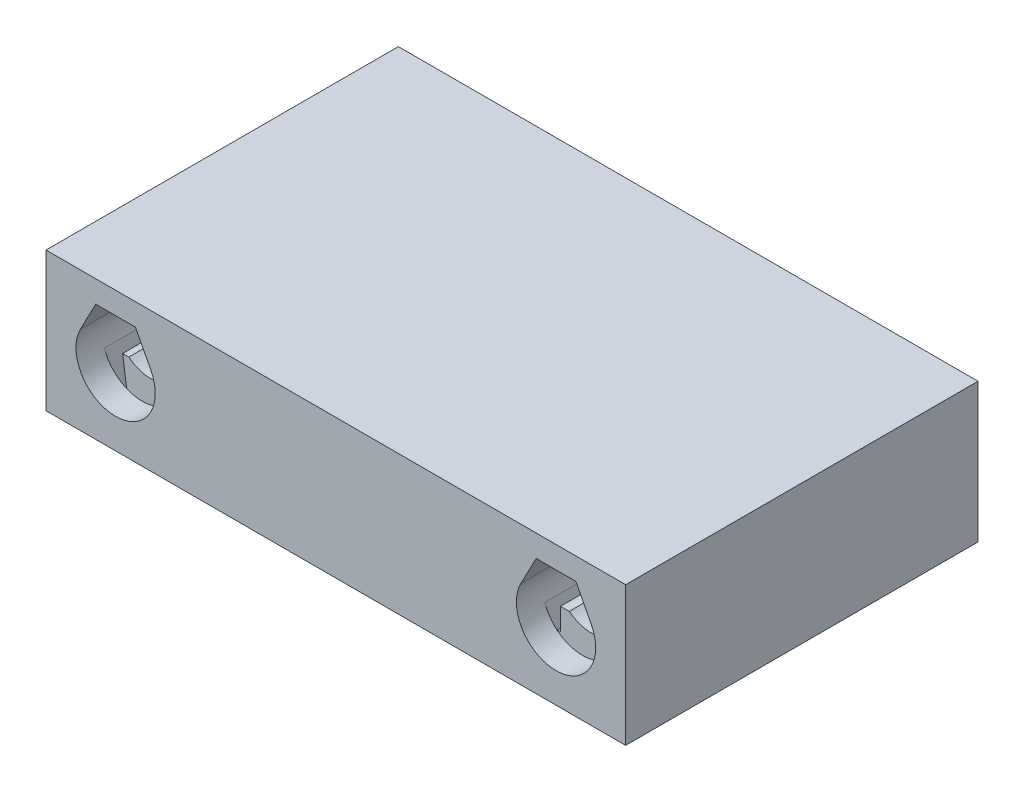
SolidWorks part; units mm, degrees
ref_plane "Piano frontale" through (0, 0, 0) normal (0, 0, 1) x (1, 0, 0)
ref_plane "Piano superiore" through (0, 0, 0) normal (0, 1, 0) x (1, 0, 0)
ref_plane "Piano destro" through (0, 0, 0) normal (1, 0, 0) x (0, 0, -1)
sketch "Schizzo2" plane through (0, 0, 0) normal (0, 0, 1) x (1, 0, 0)
  line L0 (-25, -4.5) -> (-25, 5.4) construction
  line L1 (-32.9, -7.9) -> (32.9, -7.9)
  line L2 (-32.9, -7.9) -> (-32.9, 7.9)
  line L3 (-32.9, 7.9) -> (32.9, 7.9)
  line L4 (32.9, -7.9) -> (32.9, 7.9)
  line L5 (-32.9, -7.9) -> (32.9, 7.9) construction
  line L6 (-32.9, 7.9) -> (32.9, -7.9) construction
  line L7 (0, 7.9) -> (0, -7.9) construction
  line L8 (-27.25, 5.4) -> (-22.75, 5.4)
  line L9 (-27.25, 5.4) -> (-28.9855, 2.0894)
  line L10 (-22.75, 5.4) -> (-21.0145, 2.0894)
  line L11 (27.25, 5.4) -> (22.75, 5.4)
  line L12 (22.75, 5.4) -> (21.0145, 2.0894)
  line L13 (27.25, 5.4) -> (28.9855, 2.0894)
  arc A0 (-28.9855, 2.0894) -> (-21.0145, 2.0894) centre (-25, 0) ccw
  arc A1 (28.9855, 2.0894) -> (21.0145, 2.0894) centre (25, 0) cw
  point P0 (0, 0)
  point P14 (-25, 5.4)
  dimension "D3" = 9
  dimension "D1" = 65.8
  dimension "D2" = 15.8
  dimension "D4" = 7.9
  dimension "D5" = 5.4
  dimension "D6" = 4.5
extrude "Front" add sketch "Schizzo2" along normal mid plane 3 contours L3 L4 L1 L2 | A0 L10 L8 L9 | A1 L12 L11 L13
sketch "Schizzo5" plane through (0, 0, -1.5) normal (0, 0, -1) x (-1, 0, 0)
  line L0 (-25, 5.4) -> (-25, -4.5) construction
  line L1 (-27.25, 5.4) -> (-22.75, 5.4) construction
  line L2 (-27.5, -1.9225) -> (-22.5, -1.9225) construction
  line L3 (-25, -4.5) -> (-25, -7.9) construction
  line L4 (32.9, -7.9) -> (-32.9, -7.9) construction
  line L5 (-25, -7.9) -> (-27.3599, -7.9)
  line L6 (-27.3599, -7.9) -> (-28.2, -1.9225)
  line L7 (-28.2, -1.9225) -> (-27.5, -1.9225)
  line L8 (-22.5, -1.9225) -> (-21.5, -1.9225)
  line L9 (-21.5, -1.9225) -> (-21.5, -4.4225)
  line L10 (-21.5, -4.4225) -> (-21.15, -4.4225)
  line L11 (-21.15, -4.4225) -> (-21.6387, -7.9) construction
  line L12 (-21.6387, -7.9) -> (-25, -7.9)
  line L13 (-28.3599, -7.9) -> (-29.271, -1.4172)
  line L14 (-21.15, -4.4225) -> (-20.7266, -1.4101)
  line L15 (0, -7.9) -> (0, 7.9) construction
  line L16 (32.9, 7.9) -> (-32.9, 7.9) construction
  line L17 (32.9, 7.9) -> (-32.9, 7.9)
  line L18 (-32.9, 7.9) -> (-32.9, -7.9)
  line L19 (-32.9, -7.9) -> (-28.3599, -7.9)
  line L20 (-21.6387, -7.9) -> (21.6387, -7.9)
  line L21 (-27.25, 5.4) -> (-28.9855, 2.0894) construction
  line L22 (-22.75, 5.4) -> (-21.0145, 2.0894) construction
  line L23 (-27.25, 5.4) -> (-28.9855, 2.0894)
  line L24 (-27.25, 5.4) -> (-22.75, 5.4)
  line L25 (-22.75, 5.4) -> (-21.0145, 2.0894)
  line L26 (21.15, -4.4225) -> (21.6387, -7.9) construction
  line L27 (25, -4.5) -> (25, -7.9) construction
  line L28 (27.5, -1.9225) -> (22.5, -1.9225) construction
  line L29 (25, 5.4) -> (25, -4.5) construction
  line L30 (22.75, 5.4) -> (21.0145, 2.0894)
  line L31 (27.25, 5.4) -> (22.75, 5.4)
  line L32 (27.25, 5.4) -> (28.9855, 2.0894)
  line L33 (32.9, -7.9) -> (28.3599, -7.9)
  line L34 (32.9, 7.9) -> (32.9, -7.9)
  line L35 (21.15, -4.4225) -> (20.7266, -1.4101)
  line L36 (28.3599, -7.9) -> (29.271, -1.4172)
  line L37 (21.6387, -7.9) -> (25, -7.9)
  line L38 (21.5, -4.4225) -> (21.15, -4.4225)
  line L39 (21.5, -1.9225) -> (21.5, -4.4225)
  line L40 (22.5, -1.9225) -> (21.5, -1.9225)
  line L41 (28.2, -1.9225) -> (27.5, -1.9225)
  line L42 (27.3599, -7.9) -> (28.2, -1.9225)
  line L43 (25, -7.9) -> (27.3599, -7.9)
  arc A0 (-28.9855, 2.0894) -> (-21.0145, 2.0894) centre (-25, 0) ccw construction
  arc A1 (-28.9855, 2.0894) -> (-21.0145, 2.0894) centre (-25, 0) ccw construction
  arc A2 (-27.5, -1.9225) -> (-22.5, -1.9225) centre (-25, 1.2) ccw
  arc A3 (-21.0145, 2.0894) -> (-20.7266, -1.4101) centre (-25, 0) cw
  arc A4 (28.9855, 2.0894) -> (29.271, -1.4172) centre (25, 0) cw construction
  arc A5 (21.0145, 2.0894) -> (20.7266, -1.4101) centre (25, 0) ccw
  arc A6 (27.5, -1.9225) -> (22.5, -1.9225) centre (25, 1.2) cw
  arc A7 (-28.9855, 2.0894) -> (-29.271, -1.4172) centre (-25, 0) ccw
  arc A8 (28.9855, 2.0894) -> (29.271, -1.4172) centre (25, 0) cw
  arc A9 (20.7266, -1.4101) -> (21.0145, 2.0894) centre (25, 0) cw construction
  point P12 (-25, -1.9225)
  point P55 (25, -1.9225)
  dimension "D1" = 8
  dimension "D2" = 1.2
  dimension "D3" = 98
  dimension "D4" = 0.7
  dimension "D5" = 1
  dimension "D6" = 2.5
  dimension "D7" = 5
  dimension "D8" = 0.35
  dimension "D9" = 98
  dimension "D10" = 1
  dimension "D11" = 98
extrude "Inner" add sketch "Schizzo5" along normal blind 34
sketch "Schizzo13" plane through (0, 0, -1.5) normal (0, 0, 1) x (1, 0, 0)
  line L0 (-21.5, -2.8284) -> (-21.5, -4.4225) construction
  line L1 (-21.5, -4.4225) -> (-21.15, -4.4225) construction
  line L2 (-27.3599, -7.9) -> (-27.9986, -3.3553) construction
  line L3 (-21.5, -2.8284) -> (-21.5, -4.4225)
  line L4 (-28.2, -1.9225) -> (-27.9986, -3.3553)
  line L5 (-21.5, -2.8284) -> (-21.5, -1.9225)
  line L6 (-21.5, -1.9225) -> (-22.5, -1.9225)
  line L7 (-27.5, -1.9225) -> (-28.2, -1.9225)
  line L8 (-28.2, -1.9225) -> (-27.9986, -3.3553)
  line L9 (-21.5, -2.8284) -> (-21.5, -1.9225)
  line L10 (-21.5, -1.9225) -> (-22.5, -1.9225)
  line L11 (-27.5, -1.9225) -> (-28.2, -1.9225)
  line L12 (-21.5, -4.4225) -> (-21.15, -4.4225)
  line L13 (-27.3599, -7.9) -> (-27.9986, -3.3553)
  line L14 (-32.9, -7.9) -> (32.9, -7.9) construction
  line L15 (-27.3599, -7.9) -> (-21.6387, -7.9)
  line L16 (-21.15, -4.4225) -> (-21.1554, -4.4608)
  line L17 (-21.1554, -4.4608) -> (-21.6387, -7.9)
  line L18 (-21.15, -4.4225) -> (-20.7266, -1.4101) construction
  line L19 (0, 19.3663) -> (0, -19.3663) construction
  line L20 (21.1554, -4.4608) -> (21.6387, -7.9)
  line L21 (21.15, -4.4225) -> (21.1554, -4.4608)
  line L22 (27.3599, -7.9) -> (21.6387, -7.9)
  line L23 (27.3599, -7.9) -> (27.9986, -3.3553)
  line L24 (21.5, -4.4225) -> (21.15, -4.4225)
  line L25 (27.5, -1.9225) -> (28.2, -1.9225)
  line L26 (21.5, -1.9225) -> (22.5, -1.9225)
  line L27 (21.5, -2.8284) -> (21.5, -1.9225)
  line L28 (28.2, -1.9225) -> (27.9986, -3.3553)
  line L29 (21.5, -2.8284) -> (21.5, -4.4225)
  arc A0 (27.5, -1.9225) -> (22.5, -1.9225) centre (25, 1.2) cw
  arc A2 (-27.9986, -3.3553) -> (-21.5, -2.8284) centre (-25, 0) ccw
  arc A3 (-27.5, -1.9225) -> (-22.5, -1.9225) centre (-25, 1.2) ccw
  arc A5 (-27.5, -1.9225) -> (-22.5, -1.9225) centre (-25, 1.2) ccw
  point P20 (0, 0)
  dimension "D1" = 0
extrude "Front clearance" cut sketch "Schizzo13" against normal blind 1
sketch "Schizzo12" plane through (0, 0, -35.5) normal (0, 0, -1) x (-1, 0, 0)
  line L0 (21.5, -1.9225) -> (21.5, -4.4225) construction
  line L1 (21.5, -4.4225) -> (21.15, -4.4225) construction
  line L2 (21.5, -1.9225) -> (21.5, -4.4225)
  line L4 (21.5, -4.4225) -> (21.15, -4.4225)
  line L5 (22.5, -1.9225) -> (21.5, -1.9225) construction
  line L6 (28.2, -1.9225) -> (27.5, -1.9225) construction
  line L7 (21.15, -4.4225) -> (21.6387, -7.9)
  line L8 (-27.3599, -7.9) -> (27.3599, -7.9) construction
  line L9 (21.15, -4.4225) -> (20.7266, -1.4101) construction
  line L10 (-27.3599, -7.9) -> (-21.6387, -7.9)
  line L11 (-27.3599, -7.9) -> (-28.2, -1.9225)
  line L12 (27.3599, -7.9) -> (28.2, -1.9225) construction
  line L13 (-28.2, -1.9225) -> (-27.5, -1.9225)
  line L14 (-22.5, -1.9225) -> (-21.5, -1.9225)
  line L15 (0, -7.9) -> (0, 7.9) construction
  line L16 (-21.15, -4.4225) -> (-21.6387, -7.9)
  line L17 (-21.5, -4.4225) -> (-21.15, -4.4225)
  line L18 (-21.5, -1.9225) -> (-21.5, -4.4225)
  line L20 (22.5, -1.9225) -> (21.5, -1.9225)
  line L21 (28.2, -1.9225) -> (27.5, -1.9225)
  line L22 (32.9, 7.9) -> (-32.9, 7.9) construction
  line L23 (27.3599, -7.9) -> (28.2, -1.9225)
  line L24 (27.3599, -7.9) -> (21.6387, -7.9)
  arc A0 (-22.5, -1.9225) -> (-27.5, -1.9225) centre (-25, 1.2) cw
  arc A1 (22.5, -1.9225) -> (27.5, -1.9225) centre (25, 1.2) ccw construction
  arc A3 (22.5, -1.9225) -> (27.5, -1.9225) centre (25, 1.2) ccw
extrude "Back clearance" cut sketch "Schizzo12" against normal blind 1
sketch "Schizzo7" plane through (0, 0, -35.5) normal (0, 0, -1) x (-1, 0, 0)
  line L0 (22.75, 5.4) -> (21.0145, 2.0894) construction
  line L1 (27.25, 5.4) -> (22.75, 5.4) construction
  line L2 (27.25, 5.4) -> (28.9855, 2.0894) construction
  line L3 (-27.25, 5.4) -> (-22.75, 5.4) construction
  line L4 (32.9, -7.9) -> (32.9, 7.9)
  line L5 (-32.9, -7.9) -> (32.9, -7.9)
  line L6 (-32.9, 7.9) -> (-32.9, -7.9)
  line L7 (32.9, 7.9) -> (-32.9, 7.9)
  line L8 (32.9, -7.9) -> (32.9, 7.9)
  line L9 (-32.9, -7.9) -> (32.9, -7.9)
  line L10 (-32.9, 7.9) -> (-32.9, -7.9)
  line L11 (32.9, 7.9) -> (-32.9, 7.9)
  line L12 (-22.75, 5.4) -> (-21.0145, 2.0894) construction
  line L13 (-27.25, 5.4) -> (-28.9855, 2.0894) construction
  line L14 (22.75, 5.4) -> (21.0145, 2.0894)
  line L15 (27.25, 5.4) -> (22.75, 5.4)
  line L16 (27.25, 5.4) -> (28.9855, 2.0894)
  line L17 (-27.25, 5.4) -> (-22.75, 5.4)
  line L18 (-22.75, 5.4) -> (-21.0145, 2.0894)
  line L19 (-27.25, 5.4) -> (-28.9855, 2.0894)
  arc A0 (21.0145, 2.0894) -> (28.9855, 2.0894) centre (25, 0) ccw construction
  arc A1 (-28.9855, 2.0894) -> (-21.0145, 2.0894) centre (-25, 0) ccw construction
  arc A2 (21.0145, 2.0894) -> (28.9855, 2.0894) centre (25, 0) ccw
  arc A3 (-28.9855, 2.0894) -> (-21.0145, 2.0894) centre (-25, 0) ccw
  dimension "D1" = 0
extrude "Back" add sketch "Schizzo7" along normal blind 2
sketch "Schizzo9" plane through (0, 0, -37.5) normal (0, 0, -1) x (-1, 0, 0)
  line L4 (32.9, 7.9) -> (-32.9, 7.9)
  line L5 (-32.9, 7.9) -> (-32.9, -7.9)
  line L6 (-32.9, -7.9) -> (32.9, -7.9)
  line L7 (32.9, -7.9) -> (32.9, 7.9)
  line L8 (32.9, 7.9) -> (-32.9, 7.9)
  line L9 (-32.9, 7.9) -> (-32.9, -7.9)
  line L10 (-32.9, -7.9) -> (32.9, -7.9)
  line L11 (32.9, -7.9) -> (32.9, 7.9)
  dimension "D1" = 0
extrude "Back closing" add sketch "Schizzo9" along normal blind 1
ref_axis "Rod2 axis" through (25, 1.2, -34.5) along (0, 0, 1)
ref_axis "Rod1 axis" through (-25, 1.2, -34.5) along (0, 0, 1)
